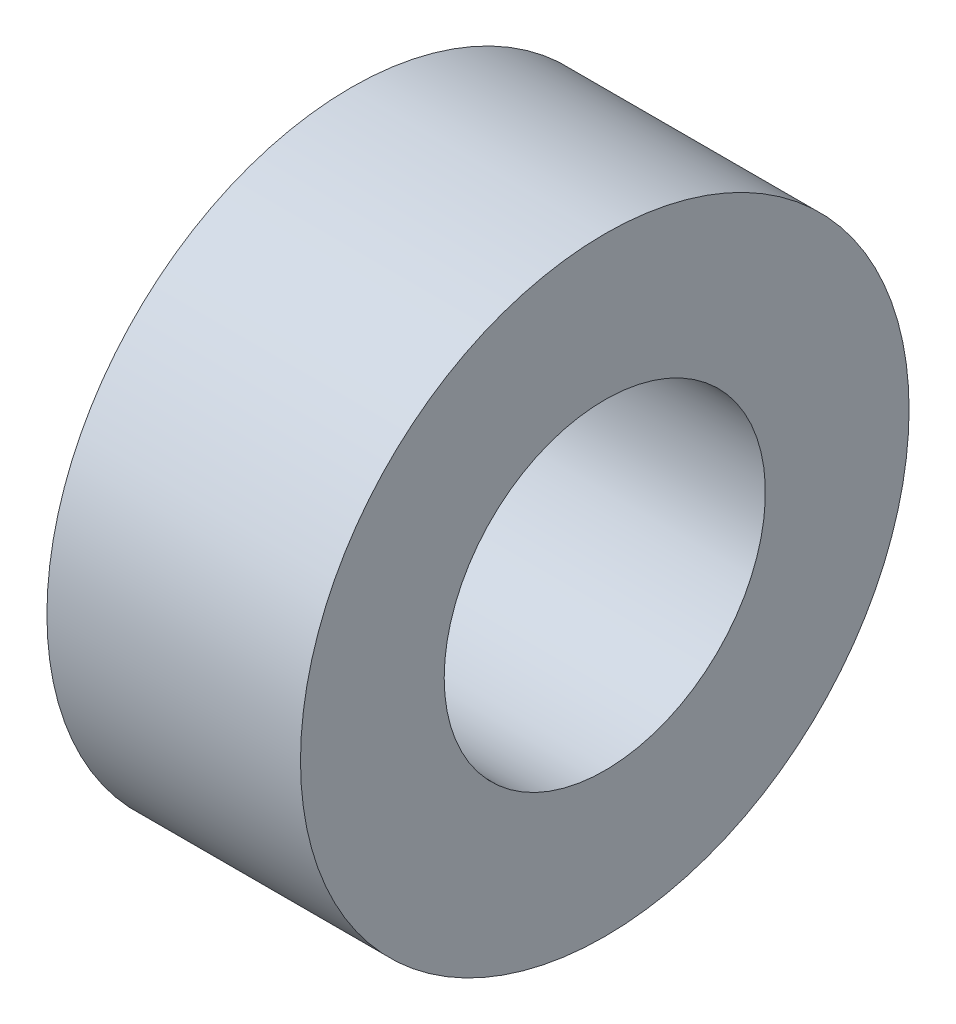
SolidWorks part; units mm, degrees
material "S235JR (1.0037)"
ref_plane "Płaszczyzna przednia" through (0, 0, 0) normal (0, 0, 1) x (1, 0, 0)
ref_plane "Płaszczyzna górna" through (0, 0, 0) normal (0, 1, 0) x (1, 0, 0)
ref_plane "Płaszczyzna prawa" through (0, 0, 0) normal (1, 0, 0) x (0, 0, -1)
sketch "Szkic1" plane through (0, 0, 0) normal (1, 0, 0) x (0, 0, -1)
  circle A0 centre (0, 0) radius 9.5
  circle A1 centre (0, 0) radius 18
  dimension "D1" = 19
  dimension "D2" = 36
extrude "Dodanie-wyciągnięcie1" add sketch "Szkic1" along normal mid plane 15
